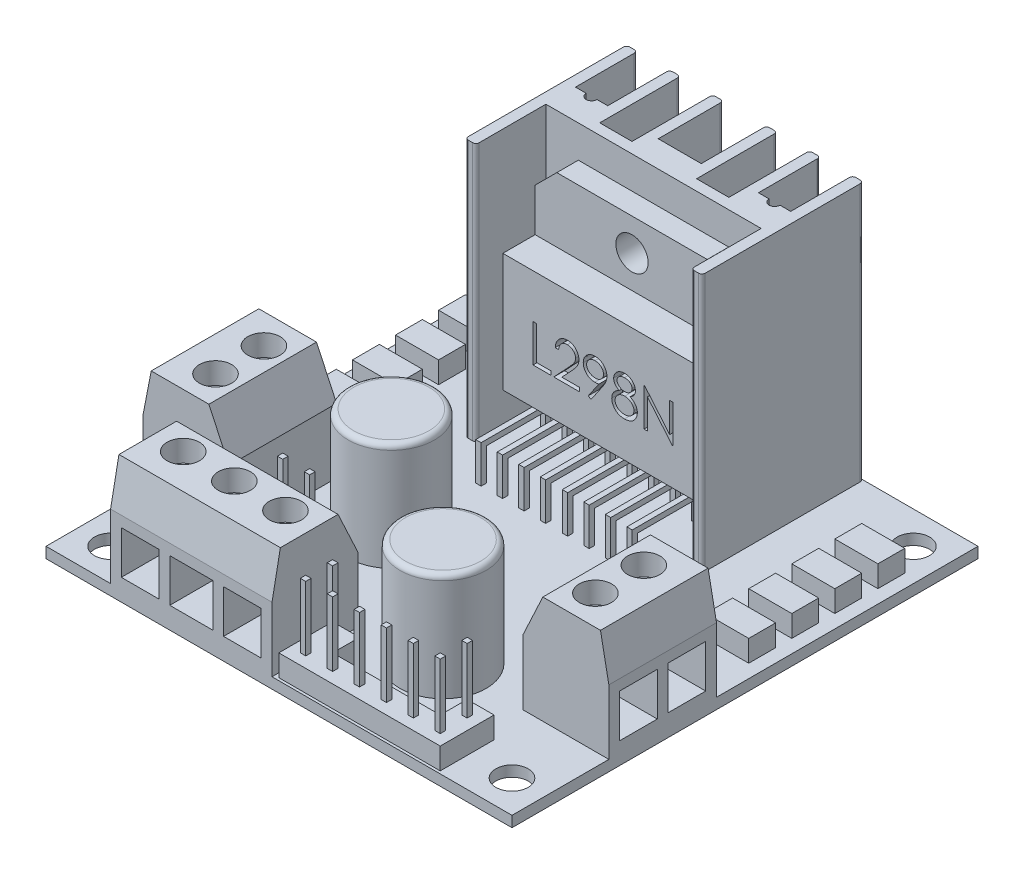
SolidWorks part; units mm, degrees
ref_plane "Alzado" through (0, 0, 0) normal (0, 0, 1) x (1, 0, 0)
ref_plane "Planta" through (0, 0, 0) normal (0, 1, 0) x (1, 0, 0)
ref_plane "Vista lateral" through (0, 0, 0) normal (1, 0, 0) x (0, 0, -1)
sketch "Croquis1" plane through (0, 0, 0) normal (0, 1, 0) x (1, 0, 0)
  line L0 (0, 0) -> (0, -43.3)
  line L1 (0, -43.3) -> (-43.3, -43.3)
  line L2 (-43.3, -43.3) -> (-43.3, 0)
  line L3 (-43.3, 0) -> (0, 0)
  line L4 (-40.3, -40.3) -> (-40.3, -3)
  line L5 (-40.3, -3) -> (-3, -3)
  line L6 (-3, -3) -> (-3, -40.3)
  line L7 (-3, -40.3) -> (-40.3, -40.3)
  circle A0 centre (-40.3, -3) radius 1.5
  circle A1 centre (-3, -3) radius 1.5
  circle A2 centre (-40.3, -40.3) radius 1.5
  circle A3 centre (-3, -40.3) radius 1.5
  dimension "D1" = 3
extrude "Saliente-Extruir1" add sketch "Croquis1" along normal blind 1 contours L3 L2 L1 L0 A3 L7 A2 L4 A0 L5 A1 L6 | A3 L6 A1 L5 A0 L4 A2 L7 region at (-0.6124, 0, 21.65) region at (-21.65, 0, 21.65)
sketch "Croquis2" plane through (0, 1, 0) normal (0, 1, 0) x (-1, 0, 0)
  line L0 (10.65, 0) -> (10.65, 15)
  line L1 (43.3, 0) -> (0, 0) construction
  line L3 (32.65, 0) -> (32.65, 15)
  line L4 (21.65, 0) -> (21.65, 15)
  line L5 (32.65, 15) -> (10.65, 15)
  line L6 (28.65, 0) -> (28.65, 15)
  line L7 (14.65, 0) -> (14.65, 15)
  line L8 (18.65, 0) -> (18.65, 15)
  line L9 (24.65, 0) -> (24.65, 15)
  line L10 (32.65, 7.5) -> (10.65, 7.5)
  line L11 (31.65, 0) -> (31.65, 15)
  line L12 (27.65, 0) -> (27.65, 15)
  line L13 (23.65, 0) -> (23.65, 15)
  line L14 (11.65, 0) -> (11.65, 15)
  line L15 (15.65, 0) -> (15.65, 15)
  line L16 (19.65, 0) -> (19.65, 15)
  line L17 (31.65, 5.7532) -> (28.65, 5.7532)
  line L18 (23.65, 6.0647) -> (19.65, 6.0647)
  line L19 (11.65, 5.7532) -> (14.65, 5.7532)
  line L20 (32.65, 8.5) -> (10.65, 8.5)
  circle A0 centre (30.15, 5.7532) radius 0.5042
  circle A1 centre (13.15, 5.7532) radius 0.5042
  line M5 (0, 0) -> (43.3, 0)
  dimension "D1" = 11
  dimension "D2" = 11
  dimension "D3" = 4
  dimension "D4" = 4
  dimension "D5" = 4
  dimension "D6" = 4
  dimension "D7" = 1
  dimension "D8" = 1
  dimension "D9" = 1
  dimension "D10" = 1
  dimension "D11" = 1
  dimension "D12" = 1
  dimension "D13" = 1
extrude "Saliente-Extruir2" add sketch "Croquis2" along normal blind 24 contours L11 L3 L10 M5 | L3 L20 L11 L10 | L20 L3 L5 L11 | L11 L20 L6 L10 | L6 L20 L12 L10 | A0 L17 L11 L10 L6 | L18 L13 L10 L4 | L18 L4 L10 L16 | L13 L9 L10 M5 | L12 L6 L10 M5 | L12 L20 L9 L10 | L9 L20 L13 L10 | L13 L20 L4 L10 | L4 L20 L16 L10 | L16 L20 L8 L10 | L16 L10 L8 M5 | L8 L20 L15 L10 | L15 L20 L7 L10 | L7 L20 L14 L10 | L20 L14 L5 L0 | L14 L20 L0 L10 | L14 L10 L0 M5 | L19 A1 L7 L10 L14 | L15 L10 L7 M5 region at (-11.15, 1, 3.75) region at (-11.15, 1, 8) region at (-11.15, 1, 11.75) region at (-13.15, 1, 8) region at (-13.15, 1, 6.681) region at (-15.15, 1, 3.75) region at (-15.15, 1, 8) region at (-17.15, 1, 8) region at (-19.15, 1, 3.75) region at (-19.15, 1, 8) region at (-20.65, 1, 8) region at (-20.65, 1, 6.7823) region at (-22.65, 1, 6.7823) region at (-22.65, 1, 8) region at (-24.15, 1, 3.75) region at (-24.15, 1, 8) region at (-26.15, 1, 8) region at (-28.15, 1, 3.75) region at (-28.15, 1, 8) region at (-30.15, 1, 6.681) region at (-30.15, 1, 8) region at (-32.15, 1, 3.75) region at (-32.15, 1, 8) region at (-32.15, 1, 11.75)
sketch "Croquis3" plane through (0, 1, 0) normal (0, 1, 0) x (-1, 0, 0)
  line L0 (43.3, 43.3) -> (0, 43.3)
  line L1 (43.3, 34.3) -> (0, 34.3)
  line L2 (43.3, 24.3) -> (0, 24.3)
  line L3 (0, 34.3) -> (0, 24.3)
  line L4 (43.3, 34.3) -> (43.3, 24.3)
  line L5 (35.3, 34.3) -> (35.3, 24.3)
  line L6 (8, 34.3) -> (8, 24.3)
  line M9 (43.3, 0) -> (43.3, 43.3)
  line M11 (0, 43.3) -> (0, 0)
  dimension "D1" = 9
  dimension "D2" = 10
  dimension "D3" = 8
  dimension "D4" = 8
extrude "Saliente-Extruir3" add sketch "Croquis3" along normal blind 10 contours L1 L5 L2 M9 | L6 L1 L2 M11 region at (-39.3, 1, 29.3) region at (-4, 1, 29.3)
chamfer "Chaflán1" distance 4 angle 25 1 edges at (-35.3, 11, 29.3) first distance on face at (-35.3, 6, 29.3)
chamfer "Chaflán2" distance 4 angle 25 1 edges at (-8, 11, 29.3) first distance on face at (-8, 6, 29.3)
chamfer "Chaflán3" distance 4 angle 11 1 edges at (0, 11, 29.3) first distance on face at (0, 3.25, 25.475)
chamfer "Chaflán4" distance 4 angle 11 1 edges at (-43.3, 11, 29.3) first distance on face at (-43.3, 3.25, 25.475)
sketch "Croquis4" plane through (0, 1, 0) normal (0, 1, 0) x (-1, 0, 0)
  line L0 (35.3, 34.3) -> (37.3, 34.3)
  line L1 (43.3, 34.3) -> (35.3, 34.3) construction
  line L2 (37.3, 34.3) -> (37.3, 43.3)
  line L3 (0, 43.3) -> (43.3, 43.3) construction
  line L4 (37.3, 43.3) -> (22.3, 43.3)
  line L5 (37.3, 35.3) -> (22.3, 35.3)
  line L6 (22.3, 35.3) -> (22.3, 43.3)
  line M24 (43.3, 43.3) -> (0, 43.3)
  dimension "D1" = 8
extrude "Saliente-Extruir4" add sketch "Croquis4" along normal blind 10 contours L6 L5 L2 M24 region at (-29.8, 1, 39.3)
chamfer "Chaflán5" distance 4 angle 11 1 edges at (-29.8, 11, 43.3) first distance on face at (-25.725, 3.25, 43.3)
chamfer "Chaflán6" distance 4 angle 25 1 edges at (-29.8, 11, 35.3) first distance on face at (-29.8, 6, 35.3)
sketch "Croquis5" plane through (0, 1, 0) normal (0, 1, 0) x (-1, 0, 0)
  line L0 (5.2392, 12.0641) -> (1.2392, 12.0641)
  line L2 (5.2392, 9.5641) -> (5.2392, 12.0641)
  line L3 (5.2392, 5.5641) -> (1.2392, 5.5641)
  line L4 (5.2392, 5.5641) -> (5.2392, 8.0641)
  line L5 (5.2392, 8.0641) -> (1.2392, 8.0641)
  line L6 (1.2392, 5.5641) -> (1.2392, 8.0641)
  line L7 (5.2392, 9.5641) -> (1.2392, 9.5641)
  line L8 (1.2392, 9.5641) -> (1.2392, 12.0641)
  line L9 (5.2392, 16.0641) -> (1.2392, 16.0641)
  line L10 (5.2392, 13.5641) -> (5.2392, 16.0641)
  line L11 (5.2392, 13.5641) -> (1.2392, 13.5641)
  line L12 (1.2392, 13.5641) -> (1.2392, 16.0641)
  line L13 (5.2392, 20.0641) -> (1.2392, 20.0641)
  line L14 (5.2392, 17.5641) -> (5.2392, 20.0641)
  line L15 (5.2392, 17.5641) -> (1.2392, 17.5641)
  line L16 (1.2392, 17.5641) -> (1.2392, 20.0641)
  line L17 (21.65, 8.5) -> (21.65, 17.5641)
  line L18 (31.65, 8.5) -> (11.65, 8.5) construction
  line L19 (42.0608, 17.5641) -> (42.0608, 20.0641)
  line L20 (38.0608, 17.5641) -> (42.0608, 17.5641)
  line L21 (38.0608, 17.5641) -> (38.0608, 20.0641)
  line L22 (38.0608, 20.0641) -> (42.0608, 20.0641)
  line L23 (42.0608, 13.5641) -> (42.0608, 16.0641)
  line L24 (38.0608, 13.5641) -> (42.0608, 13.5641)
  line L25 (38.0608, 13.5641) -> (38.0608, 16.0641)
  line L26 (38.0608, 16.0641) -> (42.0608, 16.0641)
  line L27 (42.0608, 9.5641) -> (42.0608, 12.0641)
  line L28 (38.0608, 9.5641) -> (42.0608, 9.5641)
  line L29 (42.0608, 5.5641) -> (42.0608, 8.0641)
  line L30 (38.0608, 8.0641) -> (42.0608, 8.0641)
  line L31 (38.0608, 5.5641) -> (38.0608, 8.0641)
  line L32 (38.0608, 5.5641) -> (42.0608, 5.5641)
  line L33 (38.0608, 9.5641) -> (38.0608, 12.0641)
  line L34 (38.0608, 12.0641) -> (42.0608, 12.0641)
  dimension "D1" = 4
extrude "Saliente-Extruir5" add sketch "Croquis5" along normal blind 2 contours L34 L33 L28 L27 | L31 L32 L29 L30 | L26 L25 L24 L23 | L22 L21 L20 L19 | L6 L3 L4 L5 | L8 L7 L2 L0 | L12 L11 L10 L9 | L16 L15 L14 L13 region at (-3.2392, 1, 10.8141) region at (-3.2392, 1, 6.8141) region at (-3.2392, 1, 14.8141) region at (-3.2392, 1, 18.8141) region at (-40.0608, 1, 18.8141) region at (-40.0608, 1, 14.8141) region at (-40.0608, 1, 10.8141) region at (-40.0608, 1, 6.8141)
sketch "Croquis6" plane through (0, 1, 0) normal (0, 1, 0) x (-1, 0, 0)
  line L0 (35.3, 26.21) -> (28.3, 26.21)
  line L1 (35.3, 34.3) -> (35.3, 24.3) construction
  line L2 (8, 34.3) -> (15.4066, 34.3)
  circle A0 centre (28.3, 26.21) radius 4
  circle A1 centre (15.4066, 34.3) radius 4
extrude "Saliente-Extruir6" add sketch "Croquis6" along normal blind 10 contours A0 | A1 region at (-24.4131, 1, 26.21) region at (-15.4066, 1, 30.4131)
fillet "Redondeo1" radius 0.5 2 edges at (-28.3, 11, 30.21) (-15.4066, 11, 38.3)
sketch "Croquis7" plane through (0, 1, 0) normal (0, 1, 0) x (-1, 0, 0)
  line L0 (16.9077, 40.5596) -> (16.9077, 43.0596)
  line L1 (21.9077, 40.5596) -> (19.4077, 40.5596)
  line L2 (21.9077, 40.5596) -> (21.9077, 43.0596)
  line L3 (21.9077, 43.0596) -> (19.4077, 43.0596)
  line L4 (19.4077, 40.5596) -> (19.4077, 43.0596)
  line L5 (19.4077, 40.5596) -> (16.9077, 40.5596)
  line L6 (19.4077, 43.0596) -> (16.9077, 43.0596)
  line L7 (14.4077, 40.5596) -> (14.4077, 43.0596)
  line L8 (16.9077, 40.5596) -> (14.4077, 40.5596)
  line L9 (16.9077, 43.0596) -> (14.4077, 43.0596)
  line L10 (11.9077, 40.5596) -> (11.9077, 43.0596)
  line L11 (14.4077, 40.5596) -> (11.9077, 40.5596)
  line L12 (14.4077, 43.0596) -> (11.9077, 43.0596)
  line L13 (9.4077, 40.5596) -> (9.4077, 43.0596)
  line L14 (11.9077, 40.5596) -> (9.4077, 40.5596)
  line L15 (11.9077, 43.0596) -> (9.4077, 43.0596)
  line L16 (6.9077, 40.5596) -> (6.9077, 43.0596)
  line L17 (9.4077, 40.5596) -> (6.9077, 40.5596)
  line L18 (9.4077, 43.0596) -> (6.9077, 43.0596)
  line L19 (19.4077, 38.0596) -> (19.4077, 40.5596)
  line L20 (21.9077, 38.0596) -> (19.4077, 38.0596)
  line L21 (21.9077, 40.5596) -> (19.4077, 40.5596)
  line L22 (16.9077, 38.0596) -> (16.9077, 40.5596)
  line L23 (19.4077, 38.0596) -> (16.9077, 38.0596)
  line L24 (19.4077, 40.5596) -> (16.9077, 40.5596)
  line L25 (14.4077, 38.0596) -> (14.4077, 40.5596)
  line L26 (16.9077, 38.0596) -> (14.4077, 38.0596)
  line L27 (16.9077, 40.5596) -> (14.4077, 40.5596)
  line L28 (11.9077, 38.0596) -> (11.9077, 40.5596)
  line L29 (14.4077, 38.0596) -> (11.9077, 38.0596)
  line L30 (14.4077, 40.5596) -> (11.9077, 40.5596)
  line L31 (9.4077, 38.0596) -> (9.4077, 40.5596)
  line L32 (11.9077, 38.0596) -> (9.4077, 38.0596)
  line L33 (11.9077, 40.5596) -> (9.4077, 40.5596)
  line L34 (6.9077, 38.0596) -> (6.9077, 40.5596)
  line L35 (9.4077, 38.0596) -> (6.9077, 38.0596)
  line L36 (9.4077, 40.5596) -> (6.9077, 40.5596)
  line L37 (21.9077, 38.0596) -> (21.9077, 40.5596)
  line L38 (21.9077, 40.5596) -> (21.8661, 40.5089)
  dimension "D1" = 6
  dimension "D2" = 2
extrude "Saliente-Extruir7" add sketch "Croquis7" along normal blind 2 contours L20 L37 L1 L19 | L4 L1 L2 L3 | L4 L6 L0 L5 | L0 L9 L7 L8 | L7 L12 L10 L11 | L10 L15 L13 L14 | L35 L31 L17 L34 | L13 L18 L16 L17 region at (-15.6577, 1, 41.8096) region at (-18.1577, 1, 41.8096) region at (-20.6577, 1, 41.8096) region at (-20.6577, 1, 39.3096) region at (-13.1577, 1, 41.8096) region at (-10.6577, 1, 41.8096) region at (-8.1577, 1, 41.8096) region at (-8.1577, 1, 39.3096)
sketch "Croquis8" plane through (0, 1, 0) normal (0, 1, 0) x (-1, 0, 0)
  line L0 (30.3, 34.3) -> (30.3, 31.8)
  line L1 (35.3, 34.3) -> (32.8, 34.3)
  line L2 (35.3, 34.3) -> (35.3, 31.8)
  line L3 (35.3, 31.8) -> (32.8, 31.8)
  line L4 (32.8, 34.3) -> (32.8, 31.8)
  line L5 (32.8, 34.3) -> (30.3, 34.3)
  line L6 (32.8, 31.8) -> (30.3, 31.8)
  line L7 (27.8, 34.3) -> (27.8, 31.8)
  line L8 (30.3, 34.3) -> (27.8, 34.3)
  line L9 (30.3, 31.8) -> (27.8, 31.8)
  dimension "D1" = 3
extrude "Saliente-Extruir8" add sketch "Croquis8" along normal blind 2 contours L9 L0 L8 L7 | L6 L4 L5 L0 region at (-31.55, 1, 33.05) region at (-29.05, 1, 33.05)
sketch "Croquis9" plane through (0, 3, 0) normal (0, 1, 0) x (-1, 0, 0)
  line L0 (21.9077, 43.0596) -> (6.9077, 43.0596)
  line L1 (21.9077, 41.8096) -> (6.9077, 41.8096)
  line L2 (21.9077, 43.0596) -> (21.9077, 38.0596)
  line L3 (21.9077, 38.0596) -> (19.4077, 38.0596) construction
  line L4 (21.9077, 38.0596) -> (21.9077, 43.0596) construction
  line L5 (20.6577, 43.0596) -> (20.6577, 38.0596)
  line L7 (17.9077, 42.0596) -> (17.9077, 41.5596)
  line L8 (8.1577, 38.0596) -> (8.1577, 43.0596)
  line L9 (8.1577, 38.0596) -> (8.1577, 43.0596)
  line L10 (20.4077, 42.0596) -> (20.9077, 42.0596)
  line L11 (20.4077, 42.0596) -> (20.4077, 41.5596)
  line L12 (20.4077, 41.5596) -> (20.9077, 41.5596)
  line L13 (20.9077, 42.0596) -> (20.9077, 41.5596)
  line L14 (20.4077, 42.0596) -> (20.9077, 41.5596) construction
  line L15 (20.4077, 41.5596) -> (20.9077, 42.0596) construction
  line L16 (17.9077, 41.5596) -> (18.4077, 41.5596)
  line L17 (18.4077, 42.0596) -> (18.4077, 41.5596)
  line L18 (17.9077, 42.0596) -> (18.4077, 42.0596)
  line L19 (15.4077, 42.0596) -> (15.4077, 41.5596)
  line L20 (15.4077, 41.5596) -> (15.9077, 41.5596)
  line L21 (15.9077, 42.0596) -> (15.9077, 41.5596)
  line L22 (15.4077, 42.0596) -> (15.9077, 42.0596)
  line L23 (12.9077, 42.0596) -> (12.9077, 41.5596)
  line L24 (12.9077, 41.5596) -> (13.4077, 41.5596)
  line L25 (13.4077, 42.0596) -> (13.4077, 41.5596)
  line L26 (12.9077, 42.0596) -> (13.4077, 42.0596)
  line L27 (10.4077, 42.0596) -> (10.4077, 41.5596)
  line L28 (10.4077, 41.5596) -> (10.9077, 41.5596)
  line L29 (10.9077, 42.0596) -> (10.9077, 41.5596)
  line L30 (10.4077, 42.0596) -> (10.9077, 42.0596)
  line L31 (7.9077, 42.0596) -> (7.9077, 41.5596)
  line L32 (7.9077, 41.5596) -> (8.4077, 41.5596)
  line L33 (8.4077, 42.0596) -> (8.4077, 41.5596)
  line L34 (7.9077, 42.0596) -> (8.4077, 42.0596)
  line L35 (20.4077, 39.5596) -> (20.4077, 39.0596)
  line L36 (20.4077, 39.0596) -> (20.9077, 39.0596)
  line L37 (20.9077, 39.5596) -> (20.9077, 39.0596)
  line L38 (20.4077, 39.5596) -> (20.9077, 39.5596)
  line L39 (17.9077, 39.5596) -> (17.9077, 39.0596)
  line L40 (17.9077, 39.0596) -> (18.4077, 39.0596)
  line L41 (18.4077, 39.5596) -> (18.4077, 39.0596)
  line L42 (17.9077, 39.5596) -> (18.4077, 39.5596)
  line L43 (15.4077, 39.5596) -> (15.4077, 39.0596)
  line L44 (15.4077, 39.0596) -> (15.9077, 39.0596)
  line L45 (15.9077, 39.5596) -> (15.9077, 39.0596)
  line L46 (15.4077, 39.5596) -> (15.9077, 39.5596)
  line L47 (12.9077, 39.5596) -> (12.9077, 39.0596)
  line L48 (12.9077, 39.0596) -> (13.4077, 39.0596)
  line L49 (13.4077, 39.5596) -> (13.4077, 39.0596)
  line L50 (12.9077, 39.5596) -> (13.4077, 39.5596)
  line L51 (10.4077, 39.5596) -> (10.4077, 39.0596)
  line L52 (10.4077, 39.0596) -> (10.9077, 39.0596)
  line L53 (10.9077, 39.5596) -> (10.9077, 39.0596)
  line L54 (10.4077, 39.5596) -> (10.9077, 39.5596)
  line L55 (7.9077, 39.5596) -> (7.9077, 39.0596)
  line L56 (7.9077, 39.0596) -> (8.4077, 39.0596)
  line L57 (8.4077, 39.5596) -> (8.4077, 39.0596)
  line L58 (7.9077, 39.5596) -> (8.4077, 39.5596)
  point P13 (20.6577, 41.8096)
  dimension "D4" = 6
  dimension "D1" = 1.25
  dimension "D2" = 1.25
  dimension "D3" = 1.25
  dimension "D5" = 2
extrude "Saliente-Extruir9" add sketch "Croquis9" along normal blind 6 contours L10 L11 L1 L5 | L11 L12 L5 L1 | L13 L10 L5 L1 | L13 L1 L5 L12 | L38 L35 L36 L5 | L38 L5 L36 L37 | L17 L1 L7 L16 | L18 L7 L1 L17 | L21 L1 L19 L20 | L22 L19 L1 L21 | L26 L23 L1 L25 | L25 L1 L23 L24 | L30 L27 L1 L29 | L29 L1 L27 L28 | L34 L31 L1 L9 | L31 L32 L9 L1 | L33 L1 L9 L32 | L34 L9 L1 L33 | L58 L55 L56 L9 | L58 L9 L56 L57 region at (-20.7827, 3, 39.3096) region at (-20.5327, 3, 39.3096) region at (-8.2827, 3, 39.3096) region at (-8.0327, 3, 39.3096) region at (-20.7827, 3, 41.9346) region at (-20.5327, 3, 41.9346) region at (-20.7827, 3, 41.6846) region at (-8.2827, 3, 41.9346) region at (-8.0327, 3, 41.9346) region at (-20.5327, 3, 41.6846) region at (-8.0327, 3, 41.6846) region at (-8.2827, 3, 41.6846) region at (-18.1577, 3, 41.6846) region at (-18.1577, 3, 41.9346) region at (-10.6577, 3, 41.9346) region at (-10.6577, 3, 41.6846) region at (-15.6577, 3, 41.6846) region at (-15.6577, 3, 41.9346) region at (-13.1577, 3, 41.9346) region at (-13.1577, 3, 41.6846)
sketch "Croquis10" plane through (0, 3, 0) normal (0, 1, 0) x (1, 0, 0)
  line L0 (-32.8, -34.3) -> (-27.8, -34.3)
  line L1 (-27.8, -34.3) -> (-27.8, -31.8)
  line L2 (-32.8, -33.05) -> (-27.8, -33.05)
  line L3 (-29.05, -34.3) -> (-29.05, -31.8)
  line L5 (-28.8, -33.3) -> (-28.8, -32.8)
  line L6 (-31.55, -34.3) -> (-31.55, -31.8)
  line L7 (-31.55, -34.3) -> (-31.55, -31.8)
  line L8 (-31.8, -33.3) -> (-31.3, -33.3)
  line L9 (-31.8, -33.3) -> (-31.8, -32.8)
  line L10 (-31.8, -32.8) -> (-31.3, -32.8)
  line L11 (-31.3, -33.3) -> (-31.3, -32.8)
  line L12 (-31.8, -33.3) -> (-31.3, -32.8) construction
  line L13 (-31.8, -32.8) -> (-31.3, -33.3) construction
  line L14 (-29.3, -33.3) -> (-28.8, -33.3)
  line L15 (-29.3, -32.8) -> (-28.8, -32.8)
  line L16 (-29.3, -33.3) -> (-29.3, -32.8)
  point P11 (-31.55, -33.05)
  dimension "D4" = 2
  dimension "D1" = 1.25
  dimension "D2" = 1.25
  dimension "D3" = 1.25
extrude "Saliente-Extruir10" add sketch "Croquis10" along normal blind 6 contours L11 L10 L9 L8 | L15 L5 L14 L16
sketch "Croquis11" plane through (0, 0, 8.5) normal (0, 0, 1) x (1, 0, 0)
  line L0 (-21.65, 25) -> (-21.65, 1)
  line L1 (-31.65, 25) -> (-11.65, 25) construction
  line L2 (-31.65, 1) -> (-11.65, 1) construction
  line L3 (-30.65, 25) -> (-30.65, 1)
  line L4 (-12.65, 25) -> (-12.65, 1)
  line L5 (-31.65, 22) -> (-11.65, 22)
  line L6 (-31.65, 22) -> (-11.65, 22)
  line L7 (-31.65, 15) -> (-11.65, 15)
  line L8 (-31.65, 5) -> (-11.65, 5)
  line L9 (-30.65, 19.9875) -> (-28.6375, 22)
  line L10 (-12.65, 19.9875) -> (-14.6625, 22)
  dimension "D1" = 3
  dimension "D2" = 9
  dimension "D3" = 9
  dimension "D4" = 7
  dimension "D5" = 10
extrude "Saliente-Extruir11" add sketch "Croquis11" along normal blind 5 contours L9 L3 L7 L0 L6 | L4 L10 L6 L0 L7 | L3 L8 L0 L7 | L0 L8 L4 L7 region at (-17.2772, 18.406, 8.5) region at (-26.0228, 18.406, 8.5) region at (-17.15, 10, 8.5) region at (-26.15, 10, 8.5)
sketch "Croquis12" plane through (0, 0, 13.5) normal (0, 0, 1) x (1, 0, 0)
  line L0 (-30.65, 22) -> (-12.65, 22)
  line L1 (-30.65, 16) -> (-12.65, 16)
  line L2 (-30.65, 22) -> (-30.65, 16)
  line L3 (-12.65, 22) -> (-12.65, 16)
  line L4 (-12.65, 16) -> (-12.6059, 15.8404)
  line M2 (-12.65, 5) -> (-12.65, 19.9875)
  line M3 (-12.65, 19.9875) -> (-14.6625, 22)
  line M4 (-14.6625, 22) -> (-28.6375, 22)
  line M5 (-28.6375, 22) -> (-30.65, 19.9875)
  line M6 (-30.65, 19.9875) -> (-30.65, 5)
  dimension "D1" = 6
extrude "Cortar-Extruir1" cut sketch "Croquis12" against normal blind 3 contours L1 M6 M2 M3 M4 M5 region at (-21.65, 18.9092, 13.5)
sketch "Croquis13" plane through (0, 5, 0) normal (0, -1, 0) x (1, 0, 0)
  line L0 (-30.65, 11) -> (-12.65, 11)
  line L1 (-30.65, 13.5) -> (-30.65, 8.5) construction
  line L2 (-12.65, 13.5) -> (-12.65, 8.5) construction
  line L3 (-28.4231, 11.25) -> (-27.9231, 11.25)
  line L4 (-29.4231, 11.25) -> (-28.9231, 11.25)
  line L5 (-29.4231, 11.25) -> (-29.4231, 10.75)
  line L6 (-29.4231, 10.75) -> (-28.9231, 10.75)
  line L7 (-28.9231, 11.25) -> (-28.9231, 10.75)
  line L8 (-29.4231, 11.25) -> (-28.9231, 10.75) construction
  line L9 (-29.4231, 10.75) -> (-28.9231, 11.25) construction
  line L10 (-27.9231, 11.25) -> (-27.9231, 10.75)
  line L11 (-28.4231, 10.75) -> (-27.9231, 10.75)
  line L12 (-28.4231, 11.25) -> (-28.4231, 10.75)
  line L13 (-27.4231, 11.25) -> (-26.9231, 11.25)
  line L14 (-26.9231, 11.25) -> (-26.9231, 10.75)
  line L15 (-27.4231, 10.75) -> (-26.9231, 10.75)
  line L16 (-27.4231, 11.25) -> (-27.4231, 10.75)
  line L17 (-26.4231, 11.25) -> (-25.9231, 11.25)
  line L18 (-25.9231, 11.25) -> (-25.9231, 10.75)
  line L19 (-26.4231, 10.75) -> (-25.9231, 10.75)
  line L20 (-26.4231, 11.25) -> (-26.4231, 10.75)
  line L21 (-25.4231, 11.25) -> (-24.9231, 11.25)
  line L22 (-24.9231, 11.25) -> (-24.9231, 10.75)
  line L23 (-25.4231, 10.75) -> (-24.9231, 10.75)
  line L24 (-25.4231, 11.25) -> (-25.4231, 10.75)
  line L25 (-24.4231, 11.25) -> (-23.9231, 11.25)
  line L26 (-23.9231, 11.25) -> (-23.9231, 10.75)
  line L27 (-24.4231, 10.75) -> (-23.9231, 10.75)
  line L28 (-24.4231, 11.25) -> (-24.4231, 10.75)
  line L29 (-23.4231, 11.25) -> (-22.9231, 11.25)
  line L30 (-22.9231, 11.25) -> (-22.9231, 10.75)
  line L31 (-23.4231, 10.75) -> (-22.9231, 10.75)
  line L32 (-23.4231, 11.25) -> (-23.4231, 10.75)
  line L33 (-22.4231, 11.25) -> (-21.9231, 11.25)
  line L34 (-21.9231, 11.25) -> (-21.9231, 10.75)
  line L35 (-22.4231, 10.75) -> (-21.9231, 10.75)
  line L36 (-22.4231, 11.25) -> (-22.4231, 10.75)
  line L37 (-21.65, 11) -> (-21.65, 9.6943)
  line L38 (-13.8769, 10.75) -> (-14.3769, 11.25) construction
  line L39 (-13.8769, 11.25) -> (-14.3769, 10.75) construction
  line L40 (-20.8769, 11.25) -> (-20.8769, 10.75)
  line L41 (-20.8769, 10.75) -> (-21.3769, 10.75)
  line L42 (-21.3769, 11.25) -> (-21.3769, 10.75)
  line L43 (-20.8769, 11.25) -> (-21.3769, 11.25)
  line L44 (-19.8769, 11.25) -> (-19.8769, 10.75)
  line L45 (-19.8769, 10.75) -> (-20.3769, 10.75)
  line L46 (-20.3769, 11.25) -> (-20.3769, 10.75)
  line L47 (-19.8769, 11.25) -> (-20.3769, 11.25)
  line L48 (-18.8769, 11.25) -> (-18.8769, 10.75)
  line L49 (-18.8769, 10.75) -> (-19.3769, 10.75)
  line L50 (-19.3769, 11.25) -> (-19.3769, 10.75)
  line L51 (-18.8769, 11.25) -> (-19.3769, 11.25)
  line L52 (-17.8769, 11.25) -> (-17.8769, 10.75)
  line L53 (-17.8769, 10.75) -> (-18.3769, 10.75)
  line L54 (-18.3769, 11.25) -> (-18.3769, 10.75)
  line L55 (-17.8769, 11.25) -> (-18.3769, 11.25)
  line L56 (-16.8769, 11.25) -> (-16.8769, 10.75)
  line L57 (-16.8769, 10.75) -> (-17.3769, 10.75)
  line L58 (-17.3769, 11.25) -> (-17.3769, 10.75)
  line L59 (-16.8769, 11.25) -> (-17.3769, 11.25)
  line L60 (-15.8769, 11.25) -> (-15.8769, 10.75)
  line L61 (-15.8769, 10.75) -> (-16.3769, 10.75)
  line L62 (-16.3769, 11.25) -> (-16.3769, 10.75)
  line L63 (-15.8769, 11.25) -> (-16.3769, 11.25)
  line L64 (-14.8769, 11.25) -> (-14.8769, 10.75)
  line L65 (-14.8769, 10.75) -> (-15.3769, 10.75)
  line L66 (-15.3769, 11.25) -> (-15.3769, 10.75)
  line L67 (-14.3769, 11.25) -> (-14.3769, 10.75)
  line L68 (-13.8769, 10.75) -> (-14.3769, 10.75)
  line L69 (-13.8769, 11.25) -> (-13.8769, 10.75)
  line L70 (-13.8769, 11.25) -> (-14.3769, 11.25)
  line L71 (-14.8769, 11.25) -> (-15.3769, 11.25)
  point P6 (-29.1731, 11)
  point P73 (-14.1269, 11)
  dimension "D1" = 8
extrude "Saliente-Extruir12" add sketch "Croquis13" along normal blind 1 contours L68 L67 L70 L69 | L65 L66 L71 L64 | L63 L62 L61 L60 | L59 L58 L57 L56 | L55 L54 L53 L52 | L51 L50 L49 L48 | L47 L46 L45 L44 | L43 L42 L41 L40 | L33 L34 L35 L36 | L29 L30 L31 L32 | L25 L26 L27 L28 | L21 L22 L23 L24 | L17 L18 L19 L20 | L13 L14 L15 L16 | L3 L10 L11 L12 | L4 L7 L6 L5
sketch "Croquis14" plane through (0, 0, 11.25) normal (0, 0, 1) x (1, 0, 0)
  line L0 (-14.3769, 4) -> (-14.3769, 5) construction
  line L1 (-13.8769, 4) -> (-14.3769, 4)
  line L2 (-13.8769, 4) -> (-13.8769, 4.5)
  line L3 (-13.8769, 4.5) -> (-14.3769, 4.5)
  line L4 (-14.3769, 4) -> (-14.3769, 4.5)
  line L5 (-15.8769, 4) -> (-15.8769, 4.5)
  line L6 (-15.8769, 4.5) -> (-16.3769, 4.5)
  line L7 (-16.3769, 4) -> (-16.3769, 4.5)
  line L8 (-15.8769, 4) -> (-16.3769, 4)
  line L9 (-17.8769, 4) -> (-17.8769, 4.5)
  line L10 (-17.8769, 4.5) -> (-18.3769, 4.5)
  line L11 (-18.3769, 4) -> (-18.3769, 4.5)
  line L12 (-17.8769, 4) -> (-18.3769, 4)
  line L13 (-19.8769, 4) -> (-19.8769, 4.5)
  line L14 (-19.8769, 4.5) -> (-20.3769, 4.5)
  line L15 (-20.3769, 4) -> (-20.3769, 4.5)
  line L16 (-19.8769, 4) -> (-20.3769, 4)
  line L17 (-22.4231, 4) -> (-22.4231, 5) construction
  line L18 (-21.9231, 4) -> (-22.4231, 4)
  line L19 (-21.9231, 4) -> (-21.9231, 4.5)
  line L20 (-21.9231, 4.5) -> (-22.4231, 4.5)
  line L21 (-22.4231, 4) -> (-22.4231, 4.5)
  line L22 (-23.9231, 4) -> (-23.9231, 4.5)
  line L23 (-23.9231, 4) -> (-24.4231, 4)
  line L24 (-24.4231, 4) -> (-24.4231, 4.5)
  line L25 (-23.9231, 4.5) -> (-24.4231, 4.5)
  line L26 (-25.9231, 4) -> (-25.9231, 4.5)
  line L27 (-25.9231, 4) -> (-26.4231, 4)
  line L28 (-26.4231, 4) -> (-26.4231, 4.5)
  line L29 (-25.9231, 4.5) -> (-26.4231, 4.5)
  line L30 (-27.9231, 4) -> (-27.9231, 4.5)
  line L31 (-27.9231, 4) -> (-28.4231, 4)
  line L32 (-28.4231, 4) -> (-28.4231, 4.5)
  line L33 (-27.9231, 4.5) -> (-28.4231, 4.5)
  dimension "D1" = 4
  dimension "D2" = 4
extrude "Saliente-Extruir13" add sketch "Croquis14" along normal blind 7
sketch "Croquis15" plane through (0, 0, 0) normal (0, -1, 0) x (1, 0, 0)
  line L0 (-27.9231, 18.25) -> (-27.9231, 10.75) construction
  line L1 (-28.4231, 18.25) -> (-27.9231, 18.25)
  line L2 (-28.4231, 18.25) -> (-28.4231, 17.75)
  line L3 (-28.4231, 17.75) -> (-27.9231, 17.75)
  line L4 (-27.9231, 18.25) -> (-27.9231, 17.75)
  line L5 (-25.9231, 18.25) -> (-25.9231, 17.75)
  line L6 (-26.4231, 18.25) -> (-25.9231, 18.25)
  line L7 (-26.4231, 18.25) -> (-26.4231, 17.75)
  line L8 (-26.4231, 17.75) -> (-25.9231, 17.75)
  line L9 (-23.9231, 18.25) -> (-23.9231, 17.75)
  line L10 (-24.4231, 18.25) -> (-23.9231, 18.25)
  line L11 (-24.4231, 18.25) -> (-24.4231, 17.75)
  line L12 (-24.4231, 17.75) -> (-23.9231, 17.75)
  line L13 (-21.9231, 18.25) -> (-21.9231, 17.75)
  line L14 (-22.4231, 18.25) -> (-21.9231, 18.25)
  line L15 (-22.4231, 18.25) -> (-22.4231, 17.75)
  line L16 (-22.4231, 17.75) -> (-21.9231, 17.75)
  line L17 (-19.8769, 18.25) -> (-19.8769, 10.75) construction
  line L18 (-20.3769, 18.25) -> (-19.8769, 18.25)
  line L19 (-20.3769, 18.25) -> (-20.3769, 17.75)
  line L20 (-20.3769, 17.75) -> (-19.8769, 17.75)
  line L21 (-19.8769, 18.25) -> (-19.8769, 17.75)
  line L22 (-17.8769, 18.25) -> (-17.8769, 10.75) construction
  line L23 (-18.3769, 18.25) -> (-17.8769, 18.25)
  line L24 (-18.3769, 18.25) -> (-18.3769, 17.75)
  line L25 (-18.3769, 17.75) -> (-17.8769, 17.75)
  line L26 (-17.8769, 18.25) -> (-17.8769, 17.75)
  line L27 (-15.8769, 18.25) -> (-15.8769, 10.75) construction
  line L28 (-16.3769, 18.25) -> (-15.8769, 18.25)
  line L29 (-16.3769, 18.25) -> (-16.3769, 17.75)
  line L30 (-16.3769, 17.75) -> (-15.8769, 17.75)
  line L31 (-15.8769, 18.25) -> (-15.8769, 17.75)
  line L32 (-13.8769, 18.25) -> (-13.8769, 10.75) construction
  line L33 (-14.3769, 18.25) -> (-13.8769, 18.25)
  line L34 (-14.3769, 18.25) -> (-14.3769, 17.75)
  line L35 (-14.3769, 17.75) -> (-13.8769, 17.75)
  line L36 (-13.8769, 18.25) -> (-13.8769, 17.75)
  dimension "D1" = 4
extrude "Saliente-Extruir14" add sketch "Croquis15" against normal blind 4
sketch "Croquis16" plane through (0, 0, 0) normal (0, -1, 0) x (1, 0, 0)
  line L0 (-22.9231, 11.25) -> (-22.9231, 10.75) construction
  line L1 (-29.4231, 11.25) -> (-28.9231, 11.25)
  line L2 (-29.4231, 11.25) -> (-29.4231, 10.75)
  line L3 (-29.4231, 10.75) -> (-28.9231, 10.75)
  line L4 (-28.9231, 11.25) -> (-28.9231, 10.75)
  line L5 (-27.4231, 11.25) -> (-26.9231, 11.25)
  line L6 (-27.4231, 11.25) -> (-27.4231, 10.75)
  line L7 (-27.4231, 10.75) -> (-26.9231, 10.75)
  line L8 (-26.9231, 11.25) -> (-26.9231, 10.75)
  line L9 (-25.4231, 11.25) -> (-24.9231, 11.25)
  line L10 (-25.4231, 11.25) -> (-25.4231, 10.75)
  line L11 (-25.4231, 10.75) -> (-24.9231, 10.75)
  line L12 (-24.9231, 11.25) -> (-24.9231, 10.75)
  line L13 (-23.4231, 11.25) -> (-22.9231, 11.25)
  line L14 (-23.4231, 11.25) -> (-23.4231, 10.75)
  line L15 (-23.4231, 10.75) -> (-22.9231, 10.75)
  line L16 (-22.9231, 11.25) -> (-22.9231, 10.75)
  line L18 (-21.3769, 11.25) -> (-20.8769, 11.25)
  line L19 (-21.3769, 11.25) -> (-21.3769, 10.75)
  line L20 (-21.3769, 10.75) -> (-20.8769, 10.75)
  line L21 (-20.8769, 11.25) -> (-20.8769, 10.75)
  line L22 (-19.3769, 11.25) -> (-18.8769, 11.25)
  line L23 (-19.3769, 11.25) -> (-19.3769, 10.75)
  line L24 (-19.3769, 10.75) -> (-18.8769, 10.75)
  line L25 (-18.8769, 11.25) -> (-18.8769, 10.75)
  line L26 (-17.3769, 11.25) -> (-16.8769, 11.25)
  line L27 (-17.3769, 11.25) -> (-17.3769, 10.75)
  line L28 (-17.3769, 10.75) -> (-16.8769, 10.75)
  line L29 (-16.8769, 11.25) -> (-16.8769, 10.75)
  line L30 (-15.3769, 11.25) -> (-14.8769, 11.25)
  line L31 (-15.3769, 11.25) -> (-15.3769, 10.75)
  line L32 (-15.3769, 10.75) -> (-14.8769, 10.75)
  line L33 (-14.8769, 11.25) -> (-14.8769, 10.75)
extrude "Saliente-Extruir15" add sketch "Croquis16" against normal blind 4
sketch "Croquis17" plane through (0, 0, 13.5) normal (0, 0, 1) x (1, 0, 0)
  text T0 "L298N"
extrude "Cortar-Extruir2" cut sketch "Croquis17" against normal blind 1
sketch "Croquis18" plane through (0, 0, 10.5) normal (0, 0, 1) x (1, 0, 0)
  line L2 (-14.6625, 19) -> (-28.6375, 19)
  line L3 (-14.6625, 19) -> (-28.6375, 19)
  circle A0 centre (-21.65, 19) radius 1.5
  dimension "D1" = 3
extrude "Cortar-Extruir3" cut sketch "Croquis18" against normal through all contours A0
sketch "Croquis19" plane through (0, 0, 0) normal (1, 0, 0) x (0, 0, -1)
  line L2 (-24.3, 6) -> (-34.3, 6)
  line L3 (-24.3, 6) -> (-34.3, 6)
  line L5 (-33.3, 7) -> (-33.3, 1)
  line L6 (-33.3, 7) -> (-33.3, 1)
  line L8 (-25.3, 7) -> (-25.3, 1)
  line L9 (-25.3, 7) -> (-25.3, 1)
  line L10 (-29.3, 6) -> (-29.3, 2)
  line L11 (0, 2) -> (-43.3, 2)
  line L12 (0, 2) -> (-43.3, 2)
  line L13 (-29.8, 6) -> (-29.8, 2)
  line L14 (-28.8, 6) -> (-28.8, 2)
  dimension "D1" = 1
  dimension "D2" = 1
  dimension "D3" = 1
  dimension "D4" = 2
  dimension "D5" = 0.5
  dimension "D6" = 0.5
extrude "Cortar-Extruir4" cut sketch "Croquis19" against normal blind 4 contours L13 L3 L6 L12 | L3 L14 L12 L9 region at (0, 4, 27.05) region at (0, 4, 31.55)
sketch "Croquis20" plane through (0, 0, 43.3) normal (0, 0, 1) x (1, 0, 0)
  line L2 (-22.3, 6) -> (-37.3, 6)
  line L3 (-22.3, 6) -> (-37.3, 6)
  line L5 (-36.3, 7) -> (-36.3, 1)
  line L6 (-36.3, 7) -> (-36.3, 1)
  line L8 (-23.3, 7) -> (-23.3, 1)
  line L9 (-23.3, 7) -> (-23.3, 1)
  line L10 (-26.8, 7) -> (-26.8, 1)
  line L11 (0, 2) -> (-43.3, 2)
  line L12 (0, 2) -> (-43.3, 2)
  line L13 (-32.8, 7) -> (-32.8, 1)
  line L14 (-31.8, 7) -> (-31.8, 1)
  line L15 (-27.8, 7) -> (-27.8, 1)
  dimension "D1" = 1
  dimension "D2" = 1
  dimension "D3" = 1
  dimension "D4" = 2
  dimension "D5" = 3.5
  dimension "D6" = 3.5
  dimension "D7" = 1
  dimension "D8" = 1
extrude "Cortar-Extruir5" cut sketch "Croquis20" against normal blind 4 contours L13 L3 L6 L12 | L15 L3 L14 L12 | L12 L9 L3 L10 region at (-25.05, 4, 43.3) region at (-29.8, 4, 43.3) region at (-34.55, 4, 43.3)
sketch "Croquis21" plane through (-43.3, 0, 0) normal (-1, 0, 0) x (0, 0, 1)
  line L0 (25.3, 2) -> (33.3, 2)
  line L2 (34.3, 6) -> (24.3, 6)
  line L3 (34.3, 6) -> (24.3, 6)
  line L5 (25.3, 7) -> (25.3, 1)
  line L6 (25.3, 7) -> (25.3, 1)
  line L8 (33.3, 7) -> (33.3, 1)
  line L9 (33.3, 7) -> (33.3, 1)
  line L17 (29.8, 7) -> (29.8, 1)
  line L18 (28.8, 7) -> (28.8, 1)
  line L25 (33.3, 1) -> (33.3, 6)
  line L26 (33.3, 6) -> (25.3, 6)
  line L27 (25.3, 6) -> (25.3, 1)
  line L28 (25.3, 1) -> (33.3, 1)
  line L29 (33.3, 1) -> (33.3, 6)
  line L30 (33.3, 6) -> (25.3, 6)
  line L31 (25.3, 6) -> (25.3, 1)
  line L32 (25.3, 1) -> (33.3, 1)
  dimension "D7" = 1
  dimension "D1" = 1
  dimension "D2" = 1
  dimension "D3" = 1
  dimension "D4" = 1
  dimension "D5" = 3.5
  dimension "D6" = 3.5
extrude "Cortar-Extruir6" cut sketch "Croquis21" against normal blind 4 contours L18 L3 L6 L0 | L3 L17 L0 L9 region at (-43.3, 4, 27.05) region at (-43.3, 4, 31.55)
sketch "Croquis22" plane through (0, 11, 0) normal (0, 1, 0) x (-1, 0, 0)
  line L0 (3.4561, 24.3) -> (3.4561, 34.3)
  line L1 (6.1348, 24.3) -> (0.7775, 24.3) construction
  line L2 (6.1348, 34.3) -> (0.7775, 34.3) construction
  line L3 (22.3, 39.8439) -> (37.3, 39.8439)
  line L4 (22.3, 37.1652) -> (22.3, 42.5225) construction
  line L5 (37.3, 37.1652) -> (37.3, 42.5225) construction
  line L6 (39.8439, 34.3) -> (39.8439, 24.3)
  line L7 (42.5225, 34.3) -> (37.1652, 34.3) construction
  line L8 (42.5225, 24.3) -> (37.1652, 24.3) construction
  line L9 (39.3, 28.8) -> (39.3, 25.3) construction
  line L10 (39.3, 33.3) -> (39.3, 29.8) construction
  line L11 (32.8, 39.3) -> (36.3, 39.3) construction
  line L12 (27.8, 39.3) -> (31.8, 39.3) construction
  line L13 (23.3, 39.3) -> (26.8, 39.3) construction
  line L14 (4, 29.8) -> (4, 33.3) construction
  line L15 (4, 25.3) -> (4, 28.8) construction
  circle A0 centre (39.3, 27.05) radius 1.5
  circle A1 centre (39.3, 31.55) radius 1.5
  circle A2 centre (34.55, 39.3) radius 1.5
  circle A3 centre (29.8, 39.3) radius 1.5
  circle A4 centre (25.05, 39.3) radius 1.5
  circle A5 centre (4, 31.55) radius 1.5
  circle A6 centre (4, 27.05) radius 1.5
extrude "Cortar-Extruir7" cut sketch "Croquis22" against normal blind 2 contours A0 | A1 | A2 | A3 | A4 | A5 | A6
fillet "Redondeo2" radius 0.3 16 edges at (-31.65, 13, 0) (-32.65, 13, 0) (-27.65, 13, 0) (-28.65, 13, 0) (-23.65, 13, 0) (-24.65, 13, 0) (-18.65, 13, 0) (-19.65, 13, 0) (-14.65, 13, 0) (-15.65, 13, 0) (-10.65, 13, 0) (-11.65, 13, 0) (-32.65, 13, 15) (-31.65, 13, 15) (-11.65, 13, 15) (-10.65, 13, 15) tangent propagation no
